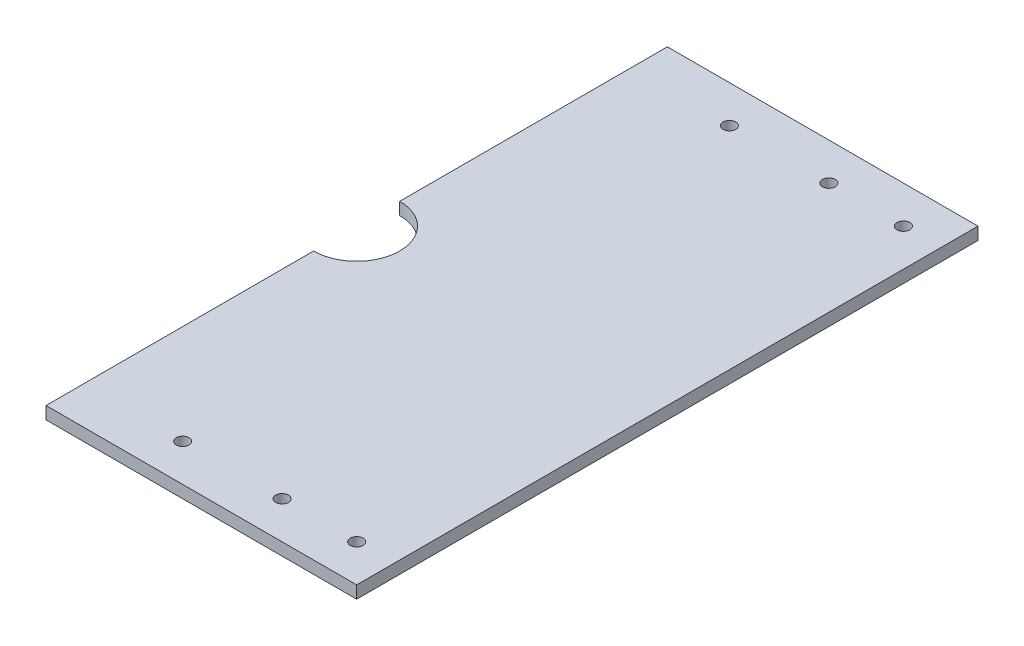
SolidWorks part; units mm, degrees
material "Copper"
ref_plane "Front Plane" through (0, 0, 0) normal (0, 0, 1) x (1, 0, 0)
ref_plane "Top Plane" through (0, 0, 0) normal (0, 1, 0) x (1, 0, 0)
ref_plane "Right Plane" through (0, 0, 0) normal (1, 0, 0) x (0, 0, -1)
sketch "Sketch1" plane through (0, 0, 0) normal (0, 1, 0) x (1, 0, 0)
  line L0 (0, -11) -> (0, -79.375)
  line L1 (0, 79.375) -> (79.37, 79.375)
  line L2 (0, 79.375) -> (0, 11)
  line L3 (0, -79.375) -> (79.37, -79.375)
  line L4 (79.37, 79.375) -> (79.37, -79.375)
  line L5 (0, 0) -> (79.37, 0) construction
  arc A0 (0, -11) -> (0, 11) centre (0, 0) ccw
  circle A1 centre (69.84, 69.845) radius 1.6319
  circle A2 centre (69.84, -69.845) radius 1.6319
  circle A3 centre (50.79, 69.845) radius 1.6319
  circle A4 centre (25.39, 69.845) radius 1.6319
  circle A5 centre (50.79, -69.845) radius 1.6319
  circle A6 centre (25.39, -69.845) radius 1.6319
  point P17 (0, 0)
  point P18 (0, 0)
  point P19 (58.3153, 71.8645)
  point P20 (25.3945, 69.4472)
  point P21 (0, 0)
  point P22 (0, 0)
  point P23 (0, 0)
  dimension "D1" = 11
  dimension "D4" = 3.2639
  dimension "D2" = 79.37
  dimension "D3" = 158.75
  dimension "D5" = 9.53
  dimension "D6" = 9.53
  dimension "D7" = 25.4
  dimension "D8" = 19.05
extrude "Boss-Extrude1" add sketch "Sketch1" along normal blind 3.175
equation "\"D6@Sketch1\"=\"D5@Sketch1\""
